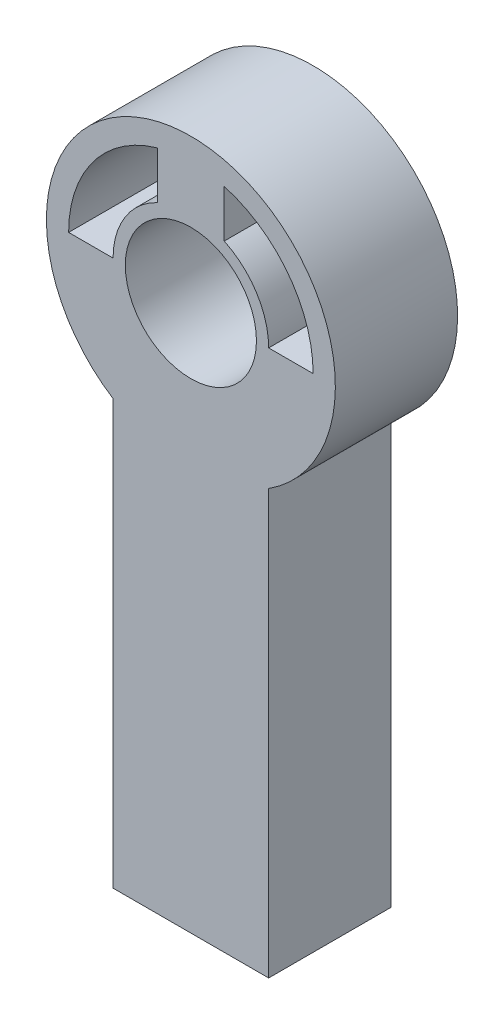
SolidWorks part; units mm, degrees
ref_plane "Front Plane" through (0, 0, 0) normal (0, 0, 1) x (1, 0, 0)
ref_plane "Top Plane" through (0, 0, 0) normal (0, 1, 0) x (1, 0, 0)
ref_plane "Right Plane" through (0, 0, 0) normal (1, 0, 0) x (0, 0, -1)
sketch "Sketch1" plane through (0, 0, 0) normal (0, 0, 1) x (1, 0, 0)
  line L0 (0, 0) -> (0, -35) construction
  line L1 (-3.5, 0) -> (-5.5, 0)
  line L2 (3.5, 0) -> (5.5, 0)
  line L3 (0, -17.5) -> (10.3868, -17.5) construction
  line L5 (-1.5, 3.1623) -> (-1.5, 5.2915)
  line L7 (1.5, 3.1623) -> (1.5, 5.2915)
  line L8 (1.5, -38.1623) -> (1.5, -40.2915)
  line L9 (-1.5, -38.1623) -> (-1.5, -40.2915)
  line L10 (3.5, -35) -> (5.5, -35)
  line L11 (-3.5, -35) -> (-5.5, -35)
  line L13 (-3.5, 0) -> (3.5, 0)
  line L14 (-3.5, 0) -> (-3.5, -35)
  line L15 (-3.5, -35) -> (3.5, -35)
  line L16 (3.5, 0) -> (3.5, -35)
  circle A0 centre (0, 0) radius 2.95
  circle A1 centre (0, 0) radius 6.5
  circle A2 centre (0, 0) radius 3.5
  circle A3 centre (0, 0) radius 5.5
  circle A4 centre (0, -35) radius 5.5
  circle A5 centre (0, -35) radius 3.5
  circle A6 centre (0, -35) radius 6.5
  circle A7 centre (0, -35) radius 2.95
  dimension "D1" = 5.9
  dimension "D2" = 13
  dimension "D3" = 11
  dimension "D4" = 7
  dimension "D5" = 35
extrude "Boss-Extrude1" add sketch "Sketch1" along normal blind 3.7 contours L14 A6 L16 A1 | A3 L16 A1 L14 | L14 A3 L16 A2 | A3 L14 A1 L16 | A6 L14 A4 L16 | A6 L16 A4 L14 | L14 A5 L16 A4 | A4 L11 L14 | A4 L16 L10 | L15 A7 A5 | L15 A7 A5 | L7 A3 L5 A2 | L1 A3 L14 | L16 A3 L2 | L13 A2 A0 | L13 A2 A0 | L8 A5 L9 A4 region at (-4.3139, -1.6382, 0) region at (-2.8919, 1.829, 0) region at (0, -3.8245, 0) region at (-3.225, -0.0783, 0) region at (-5.1348, -2.4206, 0) region at (0, -5.6156, 0) region at (0, 4.4089, 0) region at (4.3139, -1.6382, 0) region at (0, -17.5, 0) region at (0, -29.3844, 0) region at (-3.6768, -30.1401, 0) region at (0, -31.1755, 0) region at (-4.3139, -33.3618, 0) region at (0, -31.5783, 0) region at (-3.225, -35.0783, 0) region at (4.3139, -33.3618, 0) region at (0, -39.4089, 0)
sketch "Sketch2" plane through (0, 0, 0) normal (1, 0, 0) x (0, 0, -1)
  line L0 (0, 0) -> (0, -24.55) construction
  line L1 (0, -5.4772) -> (0, -29.5228) construction
  line L2 (-3.7, -5.4772) -> (-3.7, -29.5228) construction
  line L3 (-3.7, -24.55) -> (-3.1, -24.55)
  line L4 (-3.7, -24.55) -> (-3.7, -41.5)
  line L5 (-3.7, -41.5) -> (-3.1, -41.5)
  line L6 (-3.1, -24.55) -> (-3.1, -41.5)
  line L7 (-3.7, -41.5) -> (0, -41.5) construction
  dimension "D1" = 24.55
  dimension "D2" = 0.6
extrude "Cut-Extrude1" cut sketch "Sketch2" against normal blind 10 and the other way blind 10
sketch "Sketch3" plane through (0, 0, 0) normal (0, 0, -1) x (-1, 0, 0)
  circle A0 centre (0, -35) radius 2.95
  circle A1 centre (0, -35) radius 1.5
  dimension "D1" = 3
extrude "Boss-Extrude2" add sketch "Sketch3" against normal blind 3.1
sketch "Sketch4" plane through (0, 0, 0) normal (0, 0, -1) x (-1, 0, 0)
  circle A0 centre (0, -35) radius 2.5
  dimension "D1" = 5
extrude "Cut-Extrude2" cut sketch "Sketch4" against normal blind 1.5
sketch "Sketch5" plane through (0, 0, 3.1) normal (0, 0, 1) x (1, 0, 0)
  line L1 (-3.5, -24.55) -> (3.5, -24.55)
  line L2 (-3.5, -24.55) -> (-3.5, -29.5228)
  line L4 (3.5, -24.55) -> (3.5, -29.5228)
  line L5 (-5.5, -35) -> (-3.5, -35)
  line L8 (-1.5, -38.1623) -> (-1.5, -40.2915)
  line L9 (5.5, -35) -> (3.5, -35)
  line L12 (1.5, -38.1623) -> (1.5, -40.2915)
  circle A0 centre (0, -35) radius 1.5
  circle A1 centre (0, -35) radius 6.5
  circle A2 centre (0, -35) radius 3.5
  arc A3 (-5.5, -35) -> (5.5, -35) centre (0, -35) ccw
  line M2 (3.5, -35) -> (5.5, -35)
  line M4 (1.5, -40.2915) -> (1.5, -38.1623)
  arc M5 (1.5, -38.1623) -> (3.5, -35) centre (0, -35) ccw
  arc M6 (-3.5, -35) -> (-1.5, -38.1623) centre (0, -35) ccw
  line M7 (-1.5, -38.1623) -> (-1.5, -40.2915)
  line M9 (-5.5, -35) -> (-3.5, -35)
  line M10 (-3.5, -24.55) -> (-3.5, -29.5228)
  line M12 (3.5, -29.5228) -> (3.5, -24.55)
  line M13 (3.5, -24.55) -> (-3.5, -24.55)
  circle M14 centre (0, -35) radius 1.5
extrude "Boss-Extrude3" add sketch "Sketch5" along normal blind 0.4 contours A1 M12 M13 M10 | A3 A2 M2 M9 | A2 M5 M6 M14 | A3 A2 M7 M4 region at (0, -26.7003, 3.1) region at (0, -28.6838, 3.1) region at (0, -31.599, 3.1) region at (0, -39.4089, 3.1)
sketch "Sketch6" plane through (0, 0, 3.7) normal (0, 0, 1) x (1, 0, 0)
  line L0 (-1.5, 5.2915) -> (-1.5, 3.1623)
  line L2 (-3.5, -5.4772) -> (-3.5, -24.55)
  line L3 (-3.5, -24.55) -> (3.5, -24.55)
  line L4 (3.5, -5.4772) -> (3.5, -24.55)
  line L5 (1.5, 5.2915) -> (1.5, 3.1623)
  line L6 (3.5, 0) -> (5.5, 0)
  line L7 (-5.5, 0) -> (-3.5, 0)
  circle A0 centre (0, 0) radius 2.95
  arc A1 (3.5, -5.4772) -> (-3.5, -5.4772) centre (0, 0) ccw
  arc A2 (-1.5, 5.2915) -> (-5.5, 0) centre (0, 0) ccw
  arc A3 (-1.5, 3.1623) -> (-3.5, 0) centre (0, 0) ccw
  arc A4 (3.5, 0) -> (1.5, 3.1623) centre (0, 0) ccw
  arc A5 (5.5, 0) -> (1.5, 5.2915) centre (0, 0) ccw
extrude "Boss-Extrude4" add sketch "Sketch6" along normal blind 2.4
sketch "Sketch7" plane through (0, 0, 0) normal (0, 0, 1) x (1, 0, 0)
  line L1 (12.005, 7.8195) -> (-10.0995, 7.8195)
  line L2 (12.005, 7.8195) -> (12.005, -42.7273)
  line L3 (12.005, -42.7273) -> (-10.0995, -42.7273)
  line L4 (-10.0995, 7.8195) -> (-10.0995, -42.7273)
extrude "Cut-Extrude3" cut sketch "Sketch7" along normal blind 0.6
sketch "Sketch8" plane through (0, 0, 3.5) normal (0, 0, 1) x (1, 0, 0)
  line L0 (-1.5, -38.1623) -> (-1.5, -40.2915)
  line L1 (-3.5, -24.55) -> (3.5, -24.55)
  line L2 (-3.5, -24.55) -> (-3.5, -29.5228)
  line L3 (-3.5, -29.5228) -> (3.5, -29.5228)
  line L4 (3.5, -24.55) -> (3.5, -29.5228)
  line L5 (1.5, -38.1623) -> (1.5, -40.2915)
  circle A0 centre (0, -35) radius 6.5
  circle A1 centre (0, -35) radius 1.5
  circle A2 centre (0, -35) radius 5.5
  circle A3 centre (0, -35) radius 3.5
  line M1 (1.5, -40.2915) -> (1.5, -38.1623)
  arc M2 (1.5, -38.1623) -> (3.5, -35) centre (0, -35) ccw
  line M3 (3.5, -35) -> (5.5, -35)
  arc M4 (5.5, -35) -> (1.5, -40.2915) centre (0, -35) cw
  line M5 (-3.5, -24.55) -> (-3.5, -29.5228)
  arc M6 (-3.5, -29.5228) -> (3.5, -29.5228) centre (0, -35) ccw
  line M7 (3.5, -29.5228) -> (3.5, -24.55)
  line M8 (3.5, -24.55) -> (-3.5, -24.55)
  arc M9 (-1.5, -40.2915) -> (-5.5, -35) centre (0, -35) cw
  line M10 (-5.5, -35) -> (-3.5, -35)
  arc M11 (-3.5, -35) -> (-1.5, -38.1623) centre (0, -35) ccw
  line M12 (-1.5, -38.1623) -> (-1.5, -40.2915)
  circle M13 centre (0, -35) radius 1.5
extrude "Boss-Extrude5" add sketch "Sketch8" along normal blind 2.6 contours A0 M7 M8 M5 | A3 M2 M11 M13 | A3 A2 L3 M3 M10 | A2 L3 M4 M9 M6 | A3 A2 M12 M1 | L3 A2 | A2 L3 A0 region at (0, -39.4089, 3.5) region at (-2.8744, -36.8179, 3.5) region at (0, -40.6768, 3.5) region at (-4.5, -34.8771, 3.5) region at (0, -29.5137, 3.5) region at (0, -29.1095, 3.5) region at (0, -26.7003, 3.5)
sketch "Sketch9" plane through (0, 0, 6.1) normal (0, 0, 1) x (1, 0, 0)
  circle A0 centre (0, -35) radius 3.5
  circle A1 centre (0, -35) radius 5.5
extrude "Boss-Extrude6" add sketch "Sketch9" against normal blind 5.5
sketch "Sketch10" plane through (0, 0, 6.1) normal (0, 0, 1) x (1, 0, 0)
  line L1 (-3.5, -31.5) -> (3.5, -31.5)
  line L2 (-3.5, -31.5) -> (-3.5, -38.5)
  line L3 (-3.5, -38.5) -> (3.5, -38.5)
  line L4 (3.5, -31.5) -> (3.5, -38.5)
  line L5 (-3.5, -31.5) -> (3.5, -38.5) construction
  line L6 (-3.5, -38.5) -> (3.5, -31.5) construction
  dimension "D2" = 7
  dimension "D3" = 7
extrude "Cut-Extrude4" cut sketch "Sketch10" against normal blind 5.5
sketch "Sketch11" plane through (0, 0, 6.1) normal (0, 0, 1) x (1, 0, 0)
  line L0 (0, 0) -> (0, -24.55) construction
  line L2 (-9.9851, -24.55) -> (10.8803, -24.55)
  line L3 (-9.9851, -24.55) -> (-9.9851, -42.3593)
  line L4 (-9.9851, -42.3593) -> (10.8803, -42.3593)
  line L5 (10.8803, -24.55) -> (10.8803, -42.3593)
  dimension "D1" = 24.55
extrude "Cut-Extrude5" cut sketch "Sketch11" against normal blind 10
sketch "Sketch12" plane through (0, -24.55, 0) normal (0, -1, 0) x (1, 0, 0)
  line L1 (-3.5, 6.1) -> (3.5, 6.1)
  line L2 (-3.5, 6.1) -> (-3.5, 12.7524)
  line L3 (-3.5, 12.7524) -> (3.5, 12.7524)
  line L4 (3.5, 6.1) -> (3.5, 12.7524)
